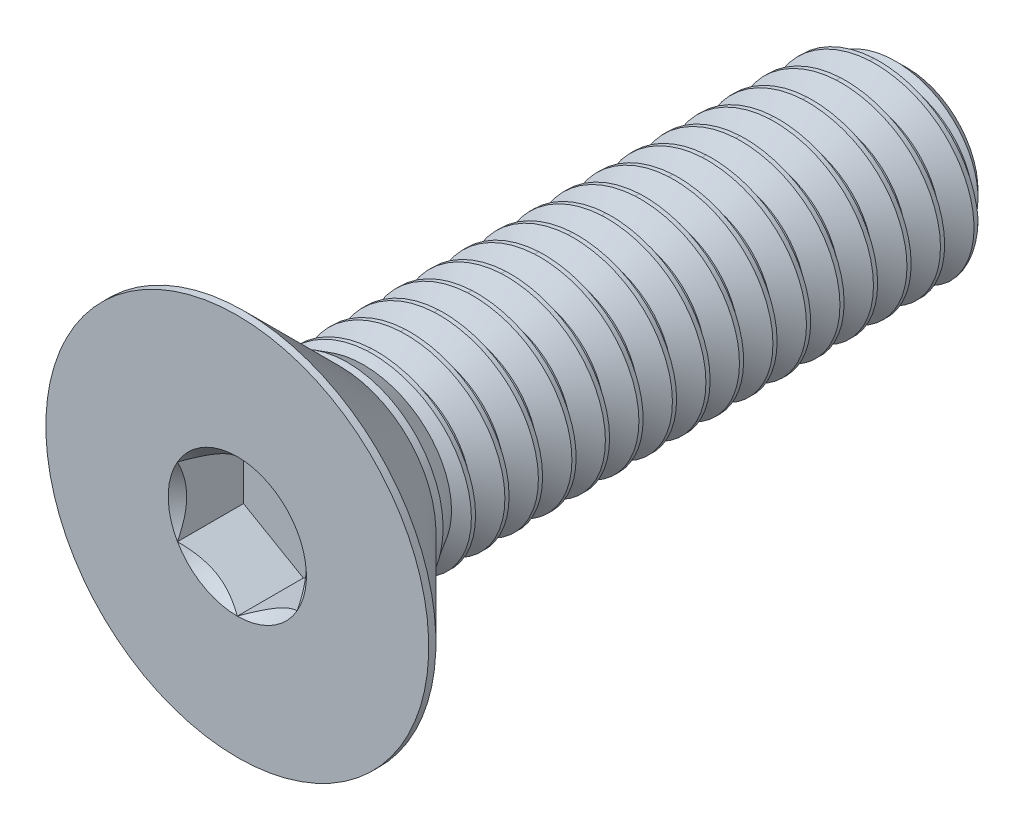
SolidWorks part; units mm, degrees
ref_plane "Front" through (0, 0, 0) normal (0, 0, 1) x (1, 0, 0)
ref_plane "Top" through (0, 0, 0) normal (0, 1, 0) x (1, 0, 0)
ref_plane "Right" through (0, 0, 0) normal (1, 0, 0) x (0, 0, -1)
sketch "Sketch1" plane through (0, 0, 0) normal (0, 0, 1) x (1, 0, 0)
  line L1 (1.25, 0.7217) -> (0, 1.4434)
  line L8 (0, 1.4434) -> (-1.25, 0.7217)
  line L9 (-1.25, 0.7217) -> (-1.25, -0.7217)
  line L10 (-1.25, -0.7217) -> (0, -1.4434)
  line L11 (0, -1.4434) -> (1.25, -0.7217)
  line L12 (1.25, -0.7217) -> (1.25, 0.7217)
  circle A0 centre (0, 0) radius 1.25 construction
  circle A1 centre (0, 0) radius 4
  point P7 (0, 4)
  dimension "Head Dia" = 8
  dimension "Hex" = 2.5
sketch "Sketch2" plane through (0, 0, 0) normal (1, 0, 0) x (0, 0, -1)
  line L2 (0, 0) -> (11.7, 0) construction
  line L3 (11.7, 0) -> (11.7, 2)
  line L6 (11.7, 2) -> (0, 2)
  line L8 (0, 2) -> (-0.15, 2)
  line L9 (-0.15, 2) -> (-2.15, 4)
  line L11 (-2.15, 4) -> (-2.3, 4)
  line L13 (-2.3, 4) -> (-2.3, 0)
  line L14 (-2.3, 0) -> (0, 0) construction
  line L15 (11.6562, 2.0758) -> (12.0062, 1.4696) construction
  line L16 (12.0062, 1.4696) -> (12.3562, 2.0758) construction
  line L17 (12.3562, 2.0758) -> (11.6562, 2.0758) construction
  line L18 (11.6781, 2.0379) -> (12.3344, 2.0379)
  line L19 (12.3344, 2.0379) -> (12.05, 1.5453)
  line L20 (12.05, 1.5453) -> (11.9625, 1.5453)
  line L21 (11.9625, 1.5453) -> (11.6781, 2.0379)
  line L22 (12.0062, 1.5453) -> (12.0062, 1.4696) construction
  line L23 (11.7, 2) -> (12.3125, 2) construction
  line L24 (12.0063, 2.0758) -> (12.0062, 2) construction
  line L25 (11.7, 1.475) -> (11.175, 2)
  line L26 (11.7, -2) -> (0, -2)
  point P28 (12.0062, 2.0379)
  point P32 (10.65, -2)
  point P33 (-0.92, 0)
  point P35 (-2.3, 4)
  dimension "Dia" = 4
  dimension "Head Ht" = 2.3
  dimension "D2" = 45
  dimension "Lg" = 14
  dimension "Pitch" = 0.7
  dimension "D3" = 0.0875
  dimension "D1" = 45
  dimension "D4" = 0.525
  dimension "D5" = 1.05
  dimension "D6" = 1.38
sketch "Sketch7" plane through (0, 0, 0) normal (1, 0, 0) x (0, 0, -1)
  line L2 (-2.3, 0) -> (-2.3, 4)
  line L3 (-2.3, 4) -> (-2.15, 4)
  line L5 (-2.15, 4) -> (-0.15, 2)
  line L6 (-0.15, 2) -> (11.175, 2)
  line L8 (11.175, 2) -> (11.7, 1.475)
  line L9 (11.7, 1.475) -> (11.7, 0)
  line L11 (11.7, 0) -> (-2.3, 0)
revolve "Revolve2" add sketch "Sketch7" angle 360 mid plane about L11
sketch "Sketch5" plane through (0, 0, 2.3) normal (0, 0, 1) x (1, 0, 0)
  line L0 (1.25, -0.7217) -> (1.25, 0.7217) construction
  line L1 (0, -1.4434) -> (1.25, -0.7217) construction
  line L2 (-1.25, -0.7217) -> (0, -1.4434) construction
  line L3 (-1.25, 0.7217) -> (-1.25, -0.7217) construction
  line L4 (0, 1.4434) -> (-1.25, 0.7217) construction
  line L5 (1.25, 0.7217) -> (0, 1.4434) construction
  line L6 (1.25, -0.7217) -> (1.25, 0.7217)
  line L7 (0, -1.4434) -> (1.25, -0.7217)
  line L8 (-1.25, -0.7217) -> (0, -1.4434)
  line L9 (-1.25, 0.7217) -> (-1.25, -0.7217)
  line L10 (0, 1.4434) -> (-1.25, 0.7217)
  line L11 (1.25, 0.7217) -> (0, 1.4434)
extrude "Cut-Extrude2" cut sketch "Sketch5" against normal up to vertex (1.38 mm away) up to point (0, 0, 0.92)
sketch "Sketch6" plane through (0, 0, 2.3) normal (0, 0, 1) x (1, 0, 0)
  circle A0 centre (0, 0) radius 1.4434
extrude "Cut-Extrude3" cut sketch "Sketch6" against normal up to vertex (1.38 mm away) draft 45 up to point (0, 0, 0.92)
sketch "Sketch3" plane through (0, 0, -11.7) normal (0, 0, -1) x (-1, 0, 0)
  circle A0 centre (0, 0) radius 2
split "Split1" trim tools "Front" bodies to split 113 resulting bodies 125 126
curve "Helix/Spiral1" pitch 0.7 height 12.4 radius 2 centre (0, 0, -11.7) axis (0, 0, 1) start towards (0, 1, 0)
sketch "Sketch8" plane through (0, 0, 0) normal (1, 0, 0) x (0, 0, -1)
  line L0 (11.6781, 2.0379) -> (12.3344, 2.0379) construction
  line L1 (11.9625, 1.5453) -> (11.6781, 2.0379) construction
  line L2 (12.05, 1.5453) -> (11.9625, 1.5453) construction
  line L3 (12.3344, 2.0379) -> (12.05, 1.5453) construction
  line L4 (11.6781, 2.0379) -> (12.3344, 2.0379)
  line L5 (11.9625, 1.5453) -> (11.6781, 2.0379)
  line L6 (12.05, 1.5453) -> (11.9625, 1.5453)
  line L7 (12.3344, 2.0379) -> (12.05, 1.5453)
sweep "Cut-Sweep1" cut profiles "Sketch8" path "Helix/Spiral1" align with end faces yes
sketch "Sketch9" plane through (0, 0, 0) normal (0, 0, 1) x (1, 0, 0)
  circle A0 centre (0, 0) radius 2
extrude "Boss-Extrude1" add sketch "Sketch9" against normal up to vertex (11.7 mm away) draft 30.9 up to point (0, 0, -11.7)
equation "\"D3@Helix/Spiral1\" =  ( \"Lg@Sketch2\" - \"Head Ht@Sketch2\" )  + \"Pitch@Sketch2\""
equation "\"D1\"= \"Head Ht@Sketch2\" * .7"
equation "\"D1\"= \"D1\""
equation "\"D4@Helix/Spiral1\" = \"Pitch@Sketch2\""
equation "\"D3@Sketch2\" = \"Pitch@Sketch2\" / 8"
equation "\"D4@Sketch2\" = \"Pitch@Sketch2\" * 0.75"
equation "\"D5@Sketch2\" = \"Pitch@Sketch2\" * 1.5"
equation "\"D6@Sketch2\" = \"Head Ht@Sketch2\" * 0.6"
